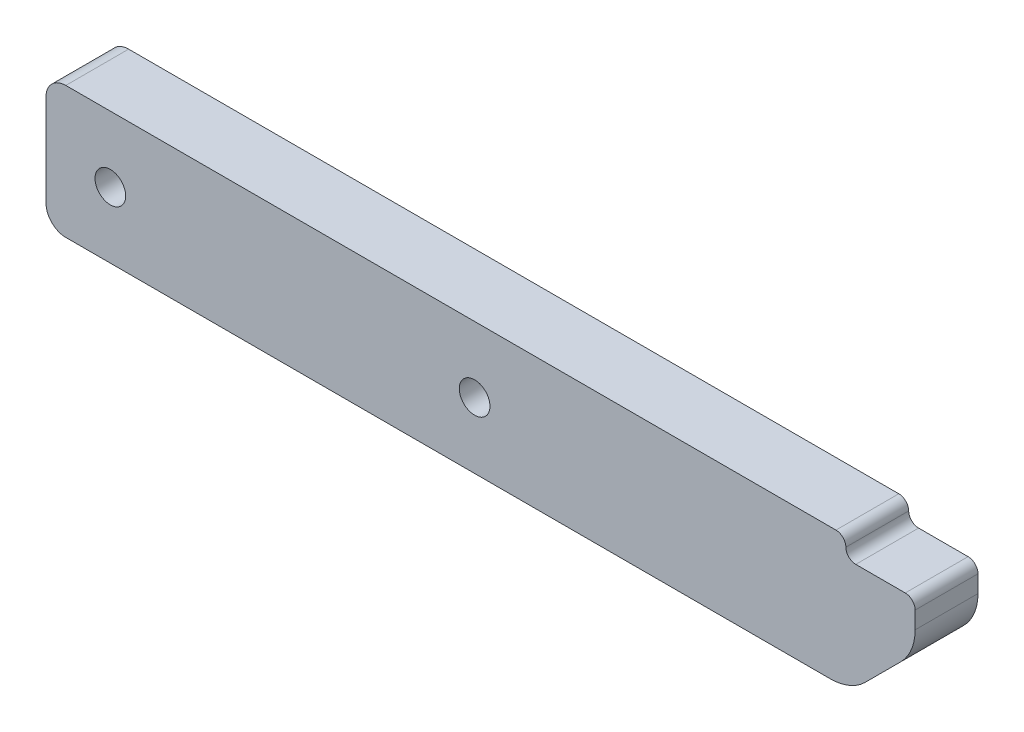
SolidWorks part; units mm, degrees
ref_plane "Front Plane" through (0, 0, 0) normal (0, 0, 1) x (1, 0, 0)
ref_plane "Top Plane" through (0, 0, 0) normal (0, 1, 0) x (1, 0, 0)
ref_plane "Right Plane" through (0, 0, 0) normal (1, 0, 0) x (0, 0, -1)
sketch "Sketch1" plane through (0, 0, 0) normal (0, 0, 1) x (1, 0, 0)
  line L1 (-38.5, -6.65) -> (36, -6.65)
  line L2 (-38.5, -6.65) -> (-38.5, 6.65)
  line L3 (-38.5, 6.65) -> (36, 6.65)
  line L4 (36, -6.65) -> (36, 6.65)
  line L7 (-38.5, 6.65) -> (-51.8, 6.65)
  line L8 (-38.5, 6.65) -> (-38.5, -6.65)
  line L9 (-38.5, -6.65) -> (-51.8, -6.65)
  line L10 (-51.8, 6.65) -> (-51.8, -6.65)
  circle A0 centre (-8.5, 0) radius 1.55
  circle A1 centre (-45.3, 0) radius 1.55
  dimension "D3" = 3.1
  dimension "D5" = 3.1
  dimension "D1" = 13.3
  dimension "D2" = 74.5
  dimension "D4" = 13.3
  dimension "D6" = 6.5
  dimension "D7" = 30
extrude "Boss-Extrude1" add sketch "Sketch1" along normal blind 6.35 contours L7 L10 L9 L2 A1 | L1 L4 L3 L2 A0 region at (-1.1944, 0, 0) region at (-45.15, -6.4619, 0)
fillet "Fillet2" radius 2 3 edges at (36, 6.65, 3.175) (-51.8, -6.65, 3.175) (-51.8, 6.65, 3.175)
chamfer "Chamfer1" distance 6.5 angle 45 1 edges at (36, -6.65, 3.175)
fillet "Fillet3" radius 5 2 edges at (29.5, -6.65, 3.175) (36, -0.15, 3.175)
sketch "Sketch2" plane through (0, 0, 6.35) normal (0, 0, 1) x (1, 0, 0)
  line L0 (34, 6.65) -> (-49.8, 6.65) construction
  line L1 (36, 4.65) -> (29, 4.65)
  line L2 (36, 4.65) -> (36, 6.65)
  line L3 (36, 6.65) -> (29, 6.65)
  line L4 (29, 4.65) -> (29, 6.65)
  dimension "D1" = 7
extrude "Cut-Extrude1" cut sketch "Sketch2" against normal through all
fillet "Fillet4" radius 1 3 edges at (29, 6.65, 3.175) (29, 4.65, 3.175) (36, 4.65, 3.175)
